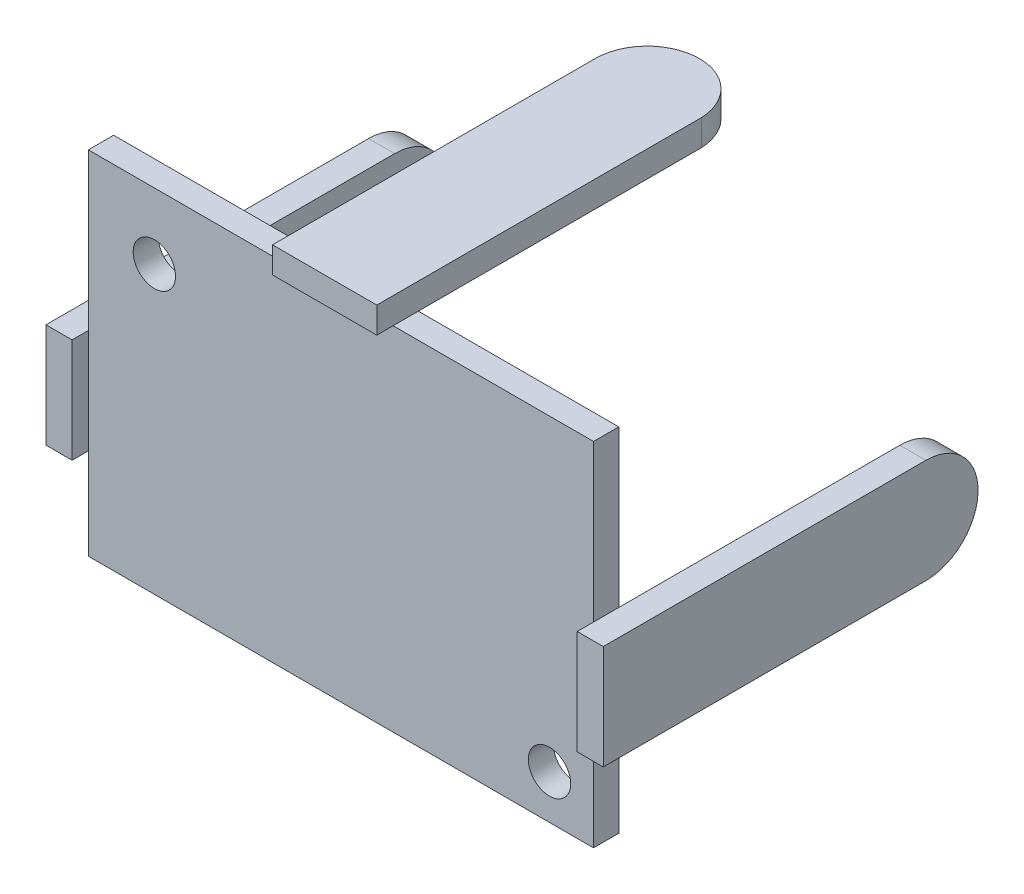
SolidWorks part; units mm, degrees
ref_plane "Front Plane" through (0, 0, 0) normal (0, 0, 1) x (1, 0, 0)
ref_plane "Top Plane" through (0, 0, 0) normal (0, 1, 0) x (1, 0, 0)
ref_plane "Right Plane" through (0, 0, 0) normal (1, 0, 0) x (0, 0, -1)
sketch "Sketch1" plane through (0, 0, 0) normal (0, 0, 1) x (1, 0, 0)
  line L0 (12.8, -8.1) -> (12.8, -10.8) construction
  line L1 (15.5, 10.8) -> (-15.5, 10.8)
  line L2 (15.5, 10.8) -> (15.5, -10.8)
  line L3 (15.5, -10.8) -> (-15.5, -10.8)
  line L4 (-15.5, 10.8) -> (-15.5, -10.8)
  line L5 (15.5, 10.8) -> (-15.5, -10.8) construction
  line L6 (15.5, -10.8) -> (-15.5, 10.8) construction
  line L7 (12.8, -8.1) -> (15.5, -8.1) construction
  circle A1 centre (12.8, -8.1) radius 1.3
  circle A2 centre (-11.45, 6.75) radius 1.3
  point P0 (0, 0)
  dimension "D3" = 1.4
  dimension "D4" = 2.6
  dimension "D5" = 2.6
  dimension "D6" = 2.75
  dimension "D7" = 1.4
  dimension "D8" = 1.4
  dimension "D1" = 21.6
  dimension "D2" = 31
  dimension "D9" = 2.75
extrude "Boss-Extrude1" add sketch "Sketch1" along normal blind 1.55
sketch "Sketch2" plane through (0, 0, 0) normal (1, 0, 0) x (0, 0, -1)
  line L0 (-1.8605, 0.7) -> (28.5002, 0.7) construction
  line L1 (-2.55, 1.2) -> (17.249, 1.2)
  line L2 (-2.55, 1.2) -> (-2.55, -5.2)
  line L3 (-2.55, -5.2) -> (17.3641, -5.2)
  line L4 (20.45, 1.2) -> (20.45, -5.2) construction
  line L5 (-1.55, -10.8) -> (0, -10.8) construction
  line L6 (-1.55, -10.8) -> (-1.55, 10.8) construction
  arc A0 (17.249, 1.2) -> (17.3641, -5.2) centre (17.249, -2.001) cw
  dimension "D6" = 3.201
  dimension "D1" = 23
  dimension "D2" = 11.5
  dimension "D3" = 0.5
  dimension "D4" = 6.4
  dimension "D5" = 1
extrude "Boss-Extrude2" add sketch "Sketch2" along normal blind 1.6 from surface starting at face at (15.5, 0, 0.775)
extrude "Boss-Extrude3" add sketch "Sketch2<2>" against normal blind 1.6 from surface starting at face at (-15.5, 0, 0.775)
sketch "Sketch2<2>" plane through (0, 0, 0) normal (1, 0, 0) x (0, 0, -1) same geometry as "Sketch2"
sketch "Sketch3" plane through (0, 10.8, 0) normal (0, 1, 0) x (1, 0, 0)
  line L0 (-2.7, -21.1313) -> (-2.7, 20.45) construction
  line L1 (-3.2, -2.55) -> (-3.2, 17.249)
  line L2 (-3.2, -2.55) -> (3.2, -2.55)
  line L3 (3.2, -2.55) -> (3.2, 17.3641)
  line L4 (-5.646, 20.45) -> (7.066, 20.45) construction
  line L5 (15.5, -1.55) -> (-15.5, -1.55) construction
  arc A0 (-3.2, 17.249) -> (3.2, 17.3641) centre (0.001, 17.249) cw
  point P15 (0, -2.55)
  dimension "D6" = 3.201
  dimension "D1" = 23
  dimension "D2" = 1
  dimension "D3" = 0.5
  dimension "D4" = 6.4
extrude "Boss-Extrude4" add sketch "Sketch3" along normal blind 1.6
